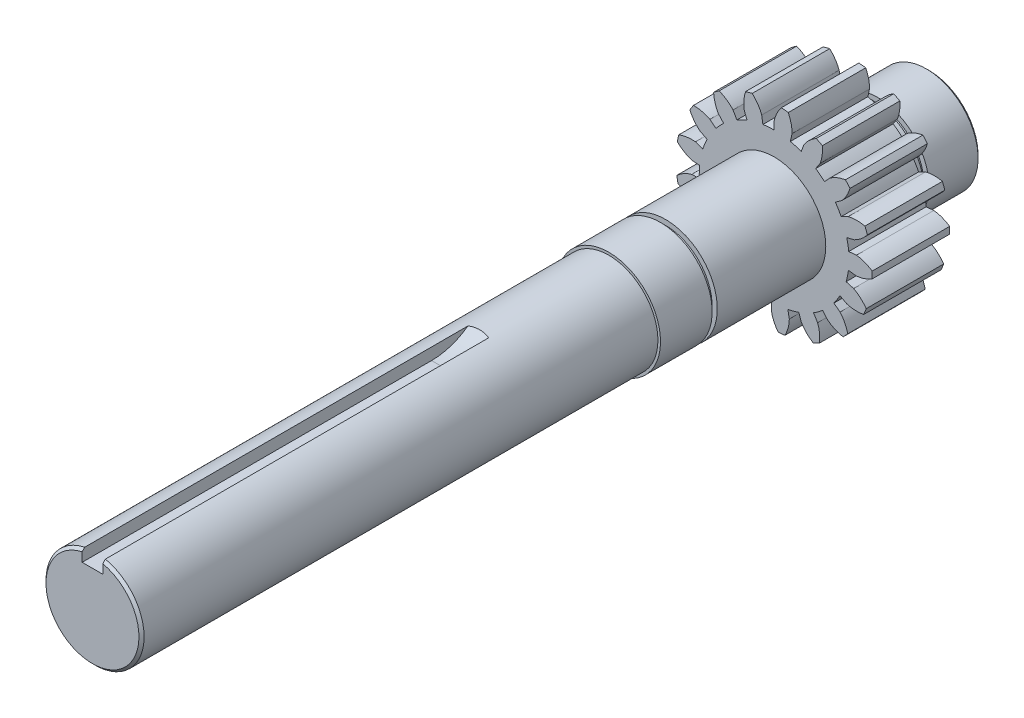
SolidWorks part; units mm, degrees
ref_plane "Front Plane" through (0, 0, 0) normal (0, 0, 1) x (1, 0, 0)
ref_plane "Top Plane" through (0, 0, 0) normal (0, 1, 0) x (1, 0, 0)
ref_plane "Right Plane" through (0, 0, 0) normal (1, 0, 0) x (0, 0, -1)
sketch "Sketch1" plane through (0, 0, 0) normal (0, 0, 1) x (1, 0, 0)
  line L0 (0, 16) -> (6.1607, 14.7664) construction
  line L1 (6.1607, 14.7664) -> (11.3714, 11.2557) construction
  line L2 (11.3714, 11.2557) -> (14.8286, 6.0094) construction
  line L3 (14.8286, 6.0094) -> (15.9992, -0.1636) construction
  line L4 (6.1607, 14.7664) -> (0.3621, 17.1856) construction
  line L5 (11.3714, 11.2557) -> (2.5314, 20.1865) construction
  line L6 (14.8286, 6.0094) -> (7.7492, 23.4784) construction
  line L7 (15.9992, -0.1636) -> (16.2562, 24.9684) construction
  line L8 (0.2868, 16.9976) -> (3.4095, 16.6546) construction
  line L9 (1.8482, 16.8261) -> (0, 0) construction
  line L10 (0, 16) -> (0, 0)
  line L11 (0, 0) -> (3.4729, 15.6185)
  circle A0 centre (0, 0) radius 16 construction
  circle A1 centre (0, 0) radius 19
  circle A2 centre (0, 0) radius 17 construction
  circle A3 centre (0, 0) radius 14.5
  spline S0 degree 3 poles (0, 16) (0.3173, 17.6369) (4.3672, 23.1974) (11.4018, 25.0265) (16.2562, 24.9684) knots 0 0 0 0 0.250277 1 1 1 1
  spline S1 degree 3 poles (3.4729, 15.6185) (3.5185, 17.2853) (0.7722, 23.5923) (-5.6977, 26.9047) (-10.449, 27.9017) knots 0 0 0 0 0.250277 1 1 1 1
  dimension "D1" = 38
  dimension "D2" = 34
  dimension "D3" = 32
  dimension "D4" = 29
  dimension "D5" = 6.283
  dimension "D6" = 6.283
  dimension "D7" = 12.566
  dimension "D8" = 18.849
  dimension "D9" = 25.132
  dimension "D10" = 3.1415
extrude "Boss-Extrude1" add sketch "Sketch1" along normal blind 15 contours L10 A3 L11 | L11 A3 L10 | L11 S1 A1 S0 L10 A3 region at (1.8009, 16.396, 0) region at (1.0533, 9.5897, 0) region at (-0.038, -0.346, 0)
pattern_circular "CirPattern1" count 17 over 360 about axis through (0, 0, 15) along (0, 0, 1) of "Boss-Extrude1"
sketch "Sketch2" plane through (0, 0, 0) normal (0, 0, -1) x (-1, 0, 0)
  circle A0 centre (0, 0) radius 10
  dimension "D1" = 20
extrude "Boss-Extrude2" add sketch "Sketch2" along normal blind 15
sketch "Sketch3" plane through (0, 0, 15) normal (0, 0, 1) x (1, 0, 0)
  circle A0 centre (0, 0) radius 10
  circle A1 centre (0, 0) radius 9.5
  dimension "D1" = 20
  dimension "D2" = 19
extrude "Boss-Extrude3" add sketch "Sketch3" along normal blind 32 contours A0
extrude "Boss-Extrude4" add sketch "Sketch3<3>" along normal blind 100 from surface contours A1 starting at face at (10, 0, 47)
sketch "Sketch3<3>" plane through (0, 0, 15) normal (0, 0, 1) x (1, 0, 0) same geometry as "Sketch3"
sketch "Sketch4" plane through (0, 0, 0) normal (1, 0, 0) x (0, 0, -1)
  line L0 (-147, 9.5) -> (-147, 7)
  line L1 (-147, 9.5) -> (-147, -9.5) construction
  line L2 (-147, 7) -> (-79.3314, 7)
  line L3 (-72, 9.5) -> (-147, 9.5)
  arc A0 (-79.3314, 7) -> (-72, 9.5) centre (-79.3314, 19) ccw
  point P8 (0, 0)
  dimension "D3" = 12
  dimension "D1" = 7
  dimension "D2" = 75
extrude "Cut-Extrude1" cut sketch "Sketch4" against normal mid plane 4
sketch "Sketch5" plane through (0, 0, 0) normal (1, 0, 0) x (0, 0, -1)
  line L0 (15, 10) -> (0, 10) construction
  line L1 (5, 10) -> (4, 10)
  line L2 (5, 10) -> (5, 9)
  line L3 (5, 9) -> (4, 9)
  line L4 (4, 10) -> (4, 9)
  line L5 (-15, 10) -> (-47, 10) construction
  line L6 (-36, 10) -> (-37, 10)
  line L7 (-36, 10) -> (-36, 9)
  line L8 (-36, 9) -> (-37, 9)
  line L9 (-37, 10) -> (-37, 9)
  line L10 (20.0024, 0) -> (-58.7861, 0) construction
  line L11 (15, -10) -> (15, 10) construction
  line L12 (-15, 10) -> (-15, -10) construction
  dimension "D1" = 1
  dimension "D2" = 1
  dimension "D3" = 18
  dimension "D4" = 18
  dimension "D5" = 10
  dimension "D6" = 21
revolve "Cut-Revolve1" cut sketch "Sketch5" angle 360 about L10
chamfer "Chamfer1" distance 0.5 angle 45 2 edges at (0, -9.5, 147) (-10, 0, -15)
